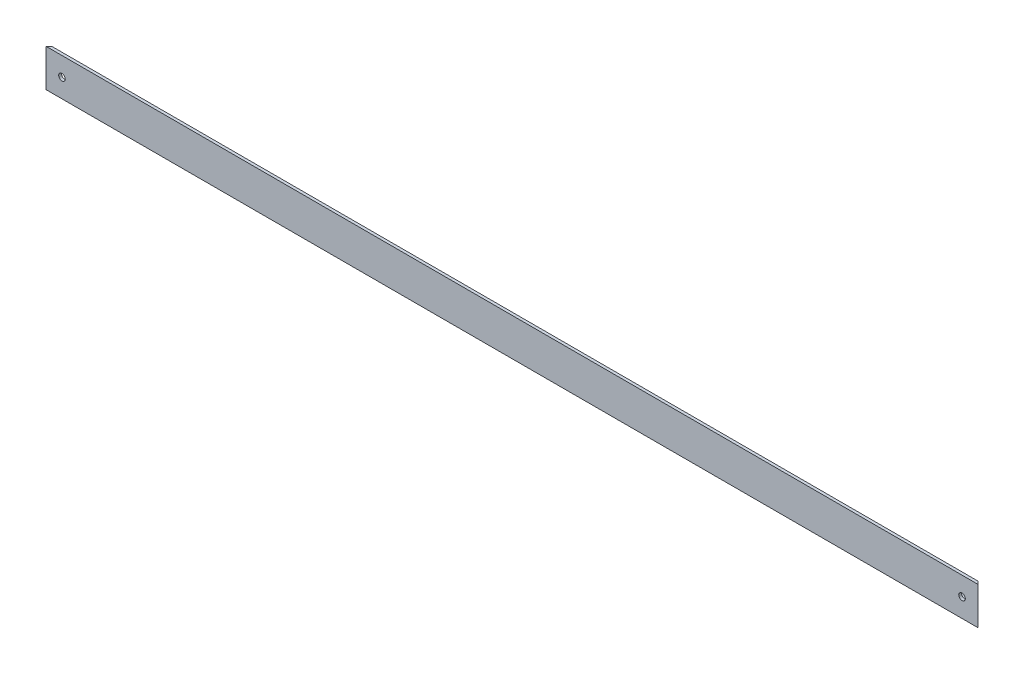
SolidWorks part; units mm, degrees
material "1060 Сплав"
ref_plane "Спереди" through (0, 0, 0) normal (0, 0, 1) x (1, 0, 0)
ref_plane "Сверху" through (0, 0, 0) normal (0, 1, 0) x (1, 0, 0)
ref_plane "Справа" through (0, 0, 0) normal (1, 0, 0) x (0, 0, -1)
sketch "Эскиз1" plane through (0, 0, 0) normal (1, 0, 0) x (0, 0, -1)
  line L0 (0, 0) -> (20, 0)
  line L1 (20, 0) -> (20, 1.5)
  line L2 (20, 1.5) -> (1.5, 1.5)
  line L3 (1.5, 1.5) -> (1.5, 20)
  line L4 (1.5, 20) -> (0, 20)
  line L5 (0, 20) -> (0, 0)
  dimension "D1" = 20
  dimension "D2" = 1.5
extrude "Бобышка-Вытянуть1" add sketch "Эскиз1" along normal blind 496
sketch "Эскиз2" plane through (0, 0, 0) normal (0, -1, 0) x (1, 0, 0)
  line L0 (0, 0) -> (0, -20)
  line L1 (0, -20) -> (20, -20)
  line L2 (496, -20) -> (0, -20) construction
  line L3 (20, -20) -> (0, 0)
extrude "Вырез-Вытянуть1" cut sketch "Эскиз2" against normal through all
sketch "Эскиз3" plane through (0, 0, 0) normal (0, 0, 1) x (1, 0, 0)
  line L0 (0, 20) -> (0, 0) construction
  circle A0 centre (8.5, 10) radius 1.75
  point P4 (0, 10)
  dimension "D1" = 3.5
  dimension "D2" = 8.5
extrude "Вырез-Вытянуть2" cut sketch "Эскиз3" against normal up to next
ref_plane "Плоскость1" through (248, 0, 0) normal (1, 0, 0) x (0, 0, -1)
mirror "Зеркальное отражение1" about plane through (248, 0, 0) normal (1, 0, 0) of "Вырез-Вытянуть2", "Вырез-Вытянуть1"
ref_axis "Ось1" through (0, 10, 0) along (1, 0, 0)
equation "\"ATX.Case.01.Dimension.1\"=499"
equation "\"D1@Эскиз1\" = \"ATX.Case.01.Profile.20.Width\""
equation "\"D2@Эскиз1\" = \"ATX.Case.01.Profile.20.Thickness\""
equation "\"D1@Бобышка-Вытянуть1\" = \"ATX.Case.01.Dimension.1\" - \"ATX.Case.01.Profile.20.Thickness\" * 2мм"
equation "\"ATX.Case.01.Profile.20.Width\"=20"
equation "\"ATX.Case.01.Profile.20.Thickness\" = 1.5"
equation "\"D2@Эскиз3\"= \"ATX.Case.01.Profile.20.Width\" / 2 - \"ATX.Case.01.Profile.20.Thickness\""
